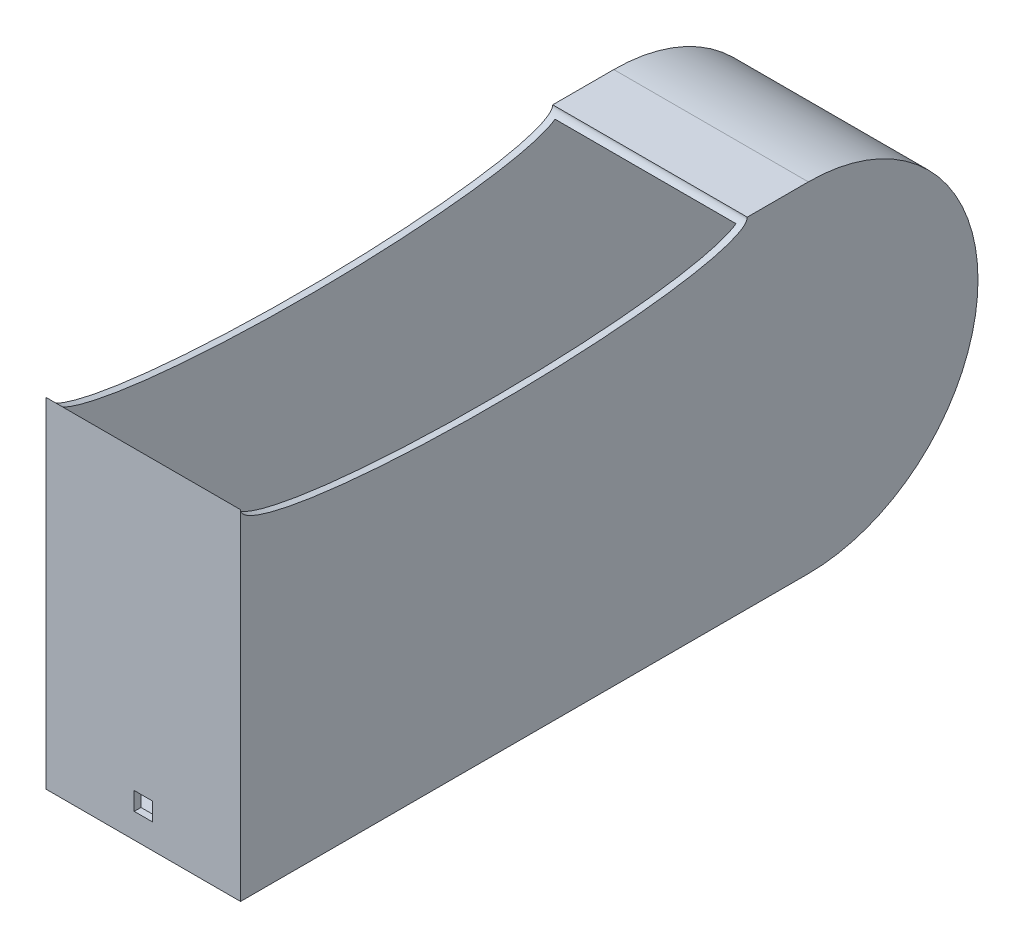
SolidWorks part; units mm, degrees
other "Markup1"
sketch "Sketch10" plane through (68.2625, 233.3625, 398.4625) normal (0.4688, 0.3088, 0.8276) x (0.8055, 0.235, -0.5439)
ref_plane "Front Plane" through (0, 0, 0) normal (0, 0, 1) x (1, 0, 0)
ref_plane "Top Plane" through (0, 0, 0) normal (0, 1, 0) x (1, 0, 0)
ref_plane "Right Plane" through (0, 0, 0) normal (1, 0, 0) x (0, 0, -1)
sketch "Sketch2" plane through (0, 0, 0) normal (1, 0, 0) x (0, 0, -1)
  line L0 (0, 0) -> (-393.7, 0)
  line L1 (-393.7, 0) -> (-393.7, 228.6)
  line L2 (-393.7, 228.6) -> (0, 228.6)
  line L4 (0, -4.7625) -> (-398.4625, -4.7625)
  line L5 (-398.4625, -4.7625) -> (-398.4625, 233.3625)
  line L6 (-398.4625, 233.3625) -> (0, 233.3625)
  arc A0 (0, 0) -> (0, 228.6) centre (0, 114.3) ccw
  arc A1 (0, -4.7625) -> (0, 233.3625) centre (0, 114.3) ccw
  dimension "D1" = 228.6
  dimension "D3" = 393.7
  dimension "D2" = 4.7625
extrude "Boss-Extrude1" add sketch "Sketch2" along normal blind 63.5 and the other way blind 63.5
sketch "Sketch4" plane through (0, 0, 398.4625) normal (0, 0, 1) x (1, 0, 0)
  line L0 (0, -130.9688) -> (0, 130.9688) construction
  line L2 (-6.35, 25.4) -> (6.35, 25.4)
  line L3 (69.85, 0) -> (-69.85, 0) construction
  line L4 (-6.35, 25.4) -> (-6.35, 12.7)
  line L5 (-6.35, 12.7) -> (6.35, 12.7)
  line L6 (6.35, 25.4) -> (6.35, 12.7)
  dimension "D3" = 12.7
  dimension "D4" = 12.7
  dimension "D5" = 12.7
  dimension "D6" = 6.35
extrude "Cut-Extrude1" cut sketch "Sketch4" against normal up to next
sketch "Sketch9" plane through (63.5, 0, 0) normal (1, 0, 0) x (0, 0, -1)
  line L0 (0, 69.85) -> (0, -69.85) construction
  line L1 (-398.4625, 233.3625) -> (0, 233.3625)
  line L2 (-398.4625, 233.3625) -> (-398.4625, -4.7625)
  line L3 (-398.4625, -4.7625) -> (0, -4.7625)
  arc A0 (0, -4.7625) -> (0, 233.3625) centre (0, 114.3) ccw
  arc A1 (0, -4.7625) -> (0, 233.3625) centre (0, 114.3) ccw construction
extrude "Boss-Extrude3" add sketch "Sketch9" along normal blind 4.7625
mirror "Mirror1" about plane through (0, 0, 0) normal (1, 0, 0) of "Boss-Extrude3"
sketch "Sketch11" plane through (0, 0, 0) normal (1, 0, 0) x (0, 0, -1)
  line L0 (0, 233.3625) -> (-398.4625, 233.3625) construction
  ellipse E0 centre (-220.6625, 233.3625) end of major axis (-398.4625, 233.3625) minor radius 25.4
  dimension "D1" = 25.4
  dimension "D2" = 177.8
extrude "Cut-Extrude2" cut sketch "Sketch11" against normal through all both and the other way through all
equation "\"fuselage_height\"=9"
equation "\"D1@Sketch2\"=\"fuselage_height\""
equation "\"fuselage_length\"=15.5"
equation "\"D3@Sketch2\"= \"fuselage_length\""
